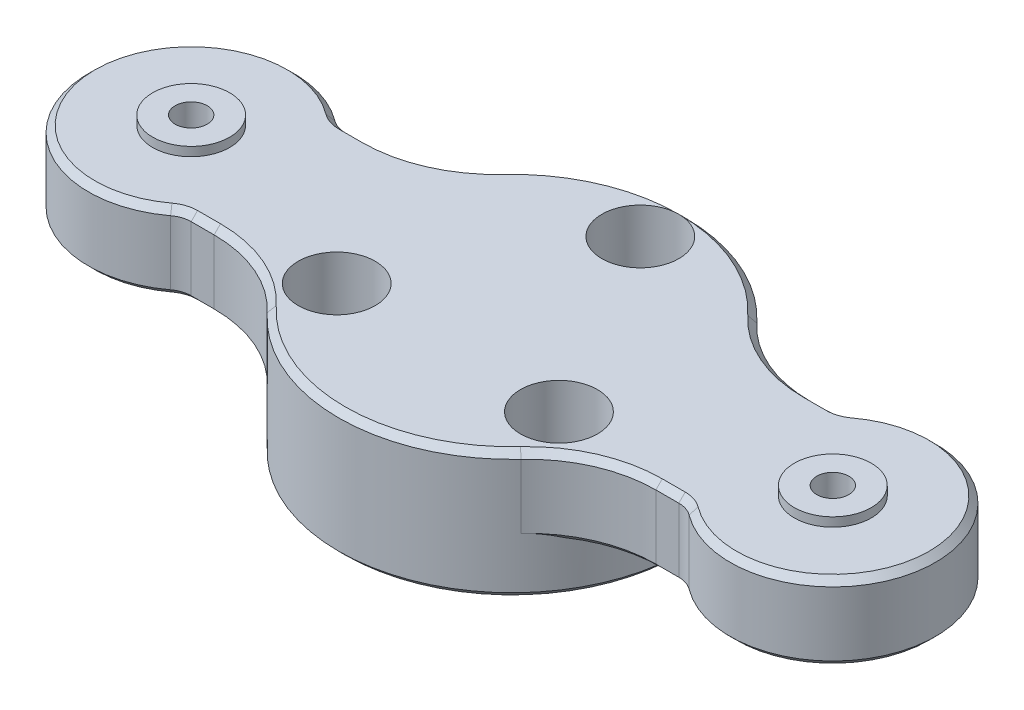
SolidWorks part; units mm, degrees
material "6061 合金"
ref_plane "Front Plane" through (0, 0, 0) normal (0, 0, 1) x (1, 0, 0)
ref_plane "Top Plane" through (0, 0, 0) normal (0, 1, 0) x (1, 0, 0)
ref_plane "Right Plane" through (0, 0, 0) normal (1, 0, 0) x (0, 0, -1)
other "Configuration Table"
sketch "草图1" plane through (0, 0, 0) normal (0, 1, 0) x (1, 0, 0)
  line L1 (0, 10) -> (-8.6603, -5) construction
  line L2 (-8.6603, -5) -> (8.6603, -5) construction
  line L3 (8.6603, -5) -> (0, 10) construction
  circle A0 centre (0, 0) radius 13.5
  circle A1 centre (0, 0) radius 10 construction
  circle A2 centre (0, 10) radius 1.6
  circle A3 centre (8.6603, -5) radius 1.6
  circle A4 centre (-8.6603, -5) radius 1.6
  point P15 (0, 0)
  dimension "D1" = 27
  dimension "D2" = 20
  dimension "D3" = 3.2
  dimension "D4" = 3
extrude "凸台-拉伸1" add sketch "草图1" along normal blind 10
sketch "草图2" plane through (0, 10, 0) normal (0, 1, 0) x (1, 0, 0)
  line L0 (-25, 0) -> (25, 0) construction
  line L1 (0, 13.5) -> (0, -13.5) construction
  line L2 (-19.7085, 6) -> (-12.0934, 6)
  line L3 (-19.7085, -6) -> (-12.0934, -6)
  line L4 (19.7085, -6) -> (12.0934, -6)
  line L5 (19.7085, 6) -> (12.0934, 6)
  arc A0 (-19.7085, 6) -> (-19.7085, -6) centre (-25, 0) ccw
  circle A1 centre (-25, 0) radius 1
  circle A2 centre (0, 0) radius 13.5 construction
  arc A3 (-12.0934, 6) -> (-12.0934, -6) centre (0, 0) ccw
  arc A4 (12.0934, -6) -> (0, 13.5) centre (0, 0) ccw
  arc A5 (12.0934, 6) -> (12.0934, -6) centre (0, 0) cw
  circle A6 centre (25, 0) radius 1
  arc A7 (19.7085, 6) -> (19.7085, -6) centre (25, 0) cw
  point P3 (0, 0)
  circle M7 centre (0, 0) radius 13.5
  dimension "D2" = 16
  dimension "D3" = 2
  dimension "D1" = 25
  dimension "D4" = 6
extrude "凸台-拉伸2" add sketch "草图2" against normal blind 6 contours L2 A0 L3 A1 M7 | A7 L5 L4 A6 M7 region at (-22.8579, 10, 0) region at (22.8579, 10, 0)
sketch "草图3" plane through (0, 10, 0) normal (0, 1, 0) x (1, 0, 0)
  circle A0 centre (0, 10) radius 3
  circle A1 centre (8.6603, -5) radius 3
  circle A2 centre (-8.6603, -5) radius 3
  dimension "D1" = 6
  dimension "D2" = 6
  dimension "D3" = 6
extrude "切除-拉伸1" cut sketch "草图3" against normal offset from surface (5 mm away) 5 up to face at (0, 0, 13.5)
sketch "草图4" plane through (0, 10, 0) normal (0, 1, 0) x (1, 0, 0)
  circle A0 centre (25, 0) radius 1 construction
  circle A1 centre (-25, 0) radius 1 construction
  circle A2 centre (25, 0) radius 1
  circle A3 centre (-25, 0) radius 1
  circle A4 centre (-25, 0) radius 3
  circle A5 centre (25, 0) radius 3
  dimension "D1" = 6
  dimension "D2" = 6
extrude "凸台-拉伸3" add sketch "草图4" along normal blind 0.7
fillet "圆角1" radius 10 4 edges at (12.0934, 7, 6) (12.0934, 7, -6) (-12.0934, 7, -6) (-12.0934, 7, 6)
fillet "圆角2" radius 2 4 edges at (19.7085, 7, -6) (19.7085, 7, 6) (-19.7085, 7, -6) (-19.7085, 7, 6)
hole_wizard "M3 螺纹孔1" positions "草图5" profile "草图6" tap size "M3" standard "GB" end condition through all
sketch "草图5" plane through (0, 10.7, 0) normal (0, 1, 0) x (1, 0, 0)
  point P0 (-25, 0)
  point P3 (25, 0)
sketch "草图6" plane through (-25, 10.7, 0) normal (1, 0, 0) x (0, 0, 1)
  line L0 (0, 0) -> (0, 10.7)
  line L1 (0, 10.7) -> (1.25, 10.7)
  line L2 (1.25, 10.7) -> (1.25, 0)
  line L5 (1.25, 0) -> (0, 0)
  line L11 (0, -6.35) -> (0, 107.95) construction
  dimension "通孔螺纹孔钻头直径" = 2.5
  dimension "通孔螺纹孔钻头深度" = 10.7
sketch "草图7" plane through (0, 0, 0) normal (0, -1, 0) x (1, 0, 0)
  line L0 (0, 10) -> (0, 0) construction
  line L1 (0, 0) -> (-8.6603, 5) construction
  line L2 (0, 0) -> (-8.6603, -5) construction
  circle A0 centre (0, 0) radius 10 construction
  circle A1 centre (0, 10) radius 1
  circle A2 centre (8.6603, -5) radius 1
  circle A3 centre (-8.6603, -5) radius 1
  point P3 (0, 10)
  point P10 (8.6603, -5)
  point P12 (-8.6603, -5)
  dimension "D1" = 20
  dimension "D2" = 2
  dimension "D3" = 60
  dimension "D5" = 60
  dimension "D4" = 3
hole_wizard "Ø2.0mm 暗销孔2" positions "草图7" profile "草图11" hole size "Ø2.0" standard "GB"
sketch "草图11" plane through (-8.6603, 0, -5) normal (1, 0, 0) x (0, 0, -1)
  line L0 (0, 0) -> (0, 6.6009)
  line L1 (0, 6.6009) -> (1, 6)
  line L2 (1, 6) -> (1, 0)
  line L5 (1, 0) -> (0, 0)
  line L10 (0, 6.6009) -> (-1, 6) construction
  line L11 (0, -6.35) -> (0, 107.95) construction
  dimension "孔直径" = 2
  dimension "孔深度" = 6
  dimension "导头角度" = 118
chamfer "倒角1" distance 0.5 angle 45 31 edges at (0, 0, 13.5) (33, 10, 0) (19.6325, 10, -6.1026) (19.6325, 10, 6.1026) (18.106, 10, -6) (18.106, 10, 6) (13.2172, 10, -6.8325) (13.2172, 10, 6.8325) (0, 10, -13.5) (0, 10, 13.5) (-13.2172, 10, -6.8325) (-13.2172, 10, 6.8325) (-18.106, 10, -6) (-18.106, 10, 6) (-19.6325, 10, -6.1026) (-19.6325, 10, 6.1026) (-33, 10, 0) (-13.2172, 4, 6.8325) (-18.106, 4, 6) (-19.6325, 4, 6.1026) (-33, 4, 0) (-19.6325, 4, -6.1026) (-18.106, 4, -6) (-13.2172, 4, -6.8325) (13.2172, 4, 6.8325) (18.106, 4, 6) (19.6325, 4, 6.1026) (33, 4, 0) (19.6325, 4, -6.1026) (13.2172, 4, -6.8325) (18.106, 4, -6)
chamfer "倒角2" distance 0.5 angle 60 3 edges at (0, 0, 9) (8.6603, 0, -6) (-8.6603, 0, -6) first distance on face at (0, 0, 13)
